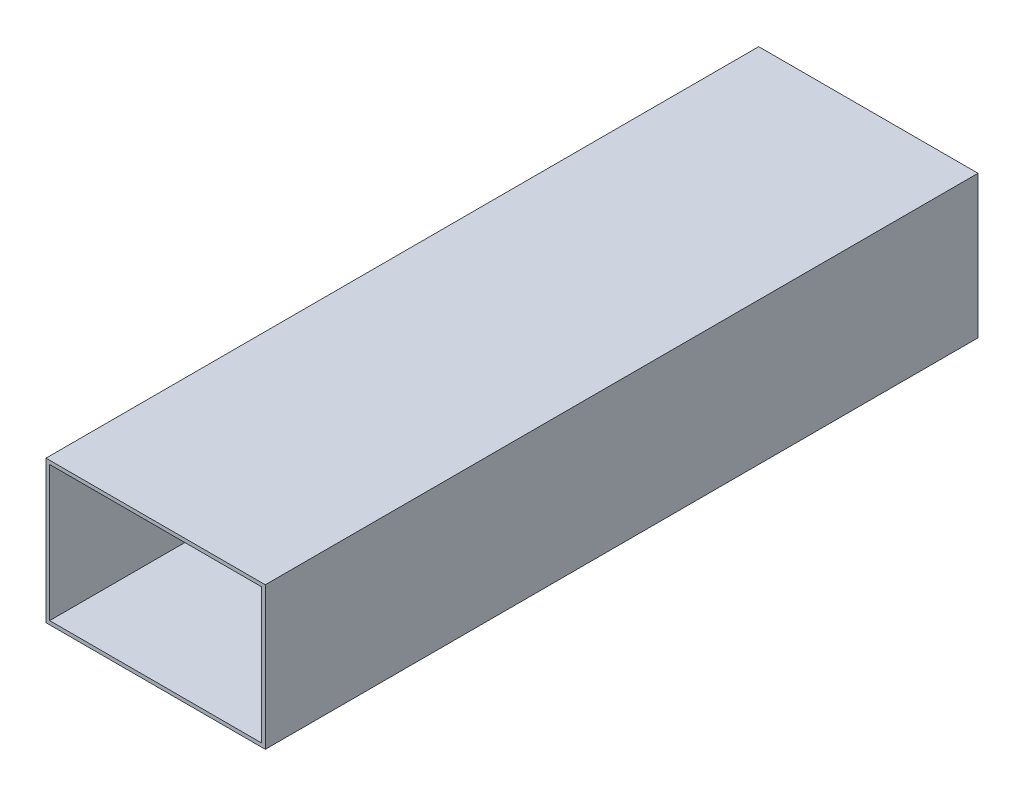
SolidWorks part; units mm, degrees
ref_plane "Front" through (0, 0, 0) normal (0, 0, 1) x (1, 0, 0)
ref_plane "Top" through (0, 0, 0) normal (0, 1, 0) x (1, 0, 0)
ref_plane "Right" through (0, 0, 0) normal (1, 0, 0) x (0, 0, -1)
sketch "Sketch1" plane through (0, 0, 0) normal (0, 1, 0) x (1, 0, 0)
  line L1 (-16.5164, 7.9953) -> (-1.5164, 7.9953)
  line L2 (-16.5164, 7.9953) -> (-16.5164, -40.7547)
  line L3 (-16.5164, -40.7547) -> (-1.5164, -40.7547)
  line L4 (-1.5164, 7.9953) -> (-1.5164, -40.7547)
extrude "Boss-Extrude1" add sketch "Sketch1" along normal blind 9.75
shell "Shell1" thickness 0.25 removed face at (-9.0164, 4.875, 40.7547)
sketch "Sketch2" [suppressed] plane through (0, 9.75, 0) normal (0, 1, 0) x (1, 0, 0)
  line L0 (-16.5164, -40.7547) -> (-1.5164, -40.7547) construction
  line L1 (-9.6664, -40.7547) -> (-8.3664, -40.7547)
  line L2 (-9.6664, -40.7547) -> (-9.6664, -34.9547)
  line L3 (-9.6664, -34.9547) -> (-8.3664, -34.9547)
  line L4 (-8.3664, -40.7547) -> (-8.3664, -34.9547)
  line L5 (-16.5164, -39.0296) -> (-9.6664, -39.0296) construction
  line L6 (-16.5164, 7.9953) -> (-16.5164, -40.7547) construction
  line L7 (-5.9164, -40.7547) -> (-4.6164, -40.7547)
  line L8 (-8.3664, -39.0296) -> (-1.5164, -39.0296) construction
  line L9 (-1.5164, -40.7547) -> (-1.5164, 7.9953) construction
  line L10 (-5.9164, -40.7547) -> (-5.9164, -34.9547)
  line L11 (-5.9164, -34.9547) -> (-4.6164, -34.9547)
  line L12 (-4.6164, -40.7547) -> (-4.6164, -34.9547)
  line L14 (-9.6664, -40.7547) -> (-8.3664, -40.7547)
  line L15 (-9.6664, -40.7547) -> (-9.6664, -34.9547)
  line L16 (-9.6664, -34.9547) -> (-8.3664, -34.9547)
  line L17 (-8.3664, -40.7547) -> (-8.3664, -34.9547)
  line L18 (-16.5164, -39.0296) -> (-9.6664, -39.0296) construction
  line L19 (-13.4164, -40.7547) -> (-12.1164, -40.7547)
  line L20 (-13.4164, -40.7547) -> (-13.4164, -34.9547)
  line L21 (-13.4164, -34.9547) -> (-12.1164, -34.9547)
  line L22 (-12.1164, -40.7547) -> (-12.1164, -34.9547)
  line L24 (-20.2664, -39.0296) -> (-13.4164, -39.0296) construction
  line L25 (-12.7664, -39.0296) -> (-5.9164, -39.0296) construction
  dimension "D1" = 2
  dimension "D2" = 2
